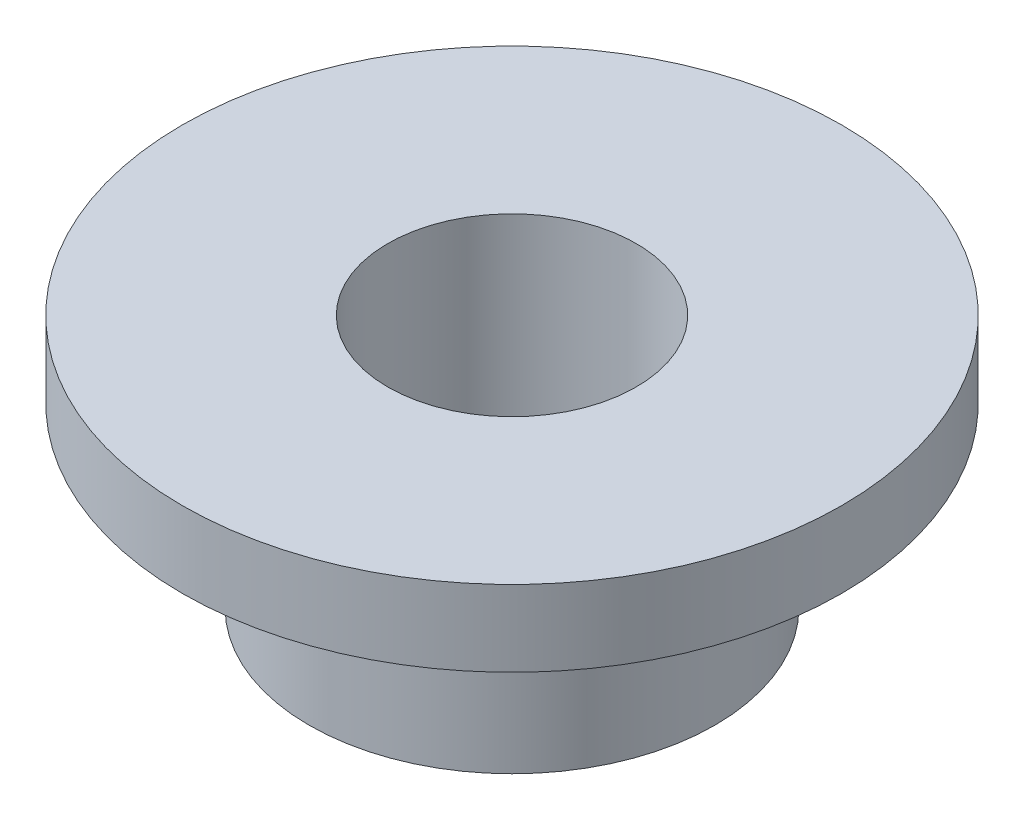
SolidWorks part; units mm, degrees
ref_plane "Front" through (0, 0, 0) normal (0, 0, 1) x (1, 0, 0)
ref_plane "Top" through (0, 0, 0) normal (0, 1, 0) x (1, 0, 0)
ref_plane "Right" through (0, 0, 0) normal (1, 0, 0) x (0, 0, -1)
sketch "Sketch1" plane through (0, 0, 0) normal (0, 1, 0) x (1, 0, 0)
  circle A0 centre (0, 0) radius 2.45
  circle A1 centre (0, 0) radius 4
  circle A2 centre (0, 0) radius 6.5
  dimension "D1" = 13
  dimension "D2" = 8
  dimension "D3" = 4.9
extrude "Boss-Extrude1" add sketch "Sketch1" along normal blind 5 contours A1 A0 region at (-3.8869, 0, 0)
extrude "Boss-Extrude2" add sketch "Sketch1<3>" along normal blind 1.5 from offset 3.5 contours A2 A1 region at (-6.3162, 0, 0)
sketch "Sketch1<3>" plane through (0, 0, 0) normal (0, 1, 0) x (1, 0, 0) same geometry as "Sketch1"
